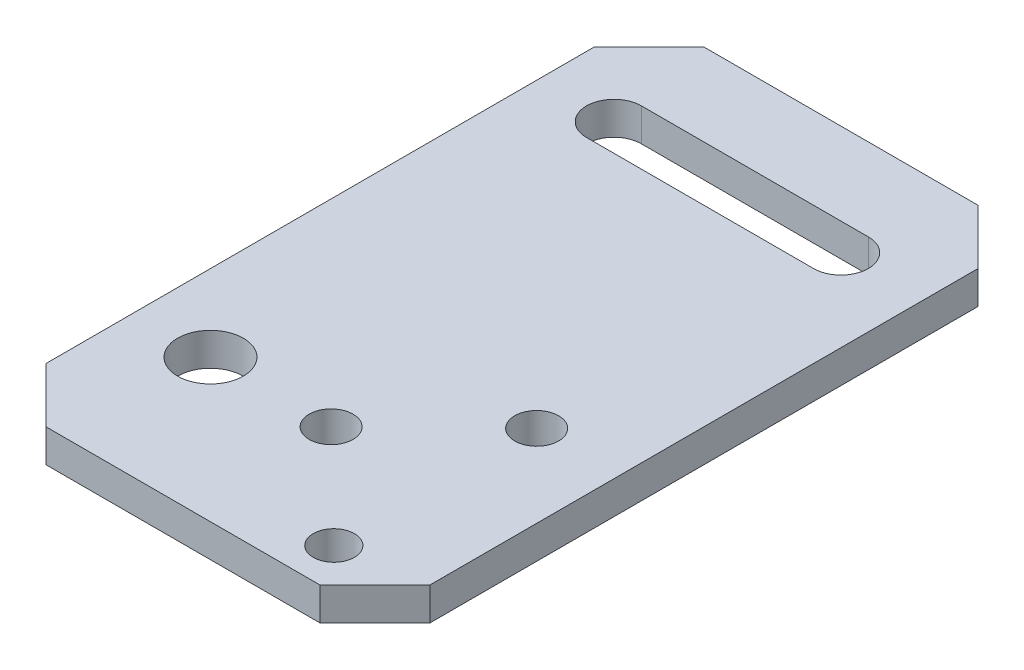
SolidWorks part; units mm, degrees
ref_plane "Alzado" through (0, 0, 0) normal (0, 0, 1) x (1, 0, 0)
ref_plane "Planta" through (0, 0, 0) normal (0, 1, 0) x (1, 0, 0)
ref_plane "Vista lateral" through (0, 0, 0) normal (1, 0, 0) x (0, 0, -1)
sketch "Croquis1" plane through (0, 0, 0) normal (0, 1, 0) x (1, 0, 0)
  line L0 (0, 0) -> (0, 34.7658) construction
  line L1 (-17.5, -30) -> (17.5, -30)
  line L2 (-17.5, -30) -> (-17.5, 30)
  line L3 (-17.5, 30) -> (17.5, 30)
  line L4 (17.5, -30) -> (17.5, 30)
  line L5 (-17.5, -30) -> (17.5, 30) construction
  line L6 (-17.5, 30) -> (17.5, -30) construction
  line L7 (10, -7.75) -> (10, -26.25) construction
  line L8 (-10.7, 17.5) -> (10, 17.5)
  line L9 (-10.7, 22.5) -> (10, 22.5)
  arc A0 (-10.7, 22.5) -> (-10.7, 17.5) centre (-10.7, 20) ccw
  arc A1 (10, 17.5) -> (10, 22.5) centre (10, 20) ccw
  circle A4 centre (-10.5, -17) radius 3
  circle A5 centre (0.5, -17) radius 2
  circle A6 centre (10, -7.75) radius 2
  circle A7 centre (10, -26.25) radius 1.8784
  point P0 (0, 0)
  point P7 (-16.9975, -30)
  point P9 (17.1721, -30.0442)
  point P10 (17.5, -30)
  point P13 (-16.1243, 28.8981)
  point P14 (17.7542, -29.5203)
  point P15 (17.8129, 33.1497)
  point P16 (17.55, 29.9128)
  point P17 (-17.6378, -29.7625)
  point P26 (10, -17)
  point P27 (-17.3353, 29.7177)
  point P28 (17.5196, 29.9661)
  dimension "D5" = 5
  dimension "D9" = 6
  dimension "D12" = 4
  dimension "D15" = 4
  dimension "D1" = 35
  dimension "D2" = 60
  dimension "D3" = 10.7
  dimension "D4" = 10
  dimension "D6" = 10
  dimension "D8" = 7
  dimension "D10" = 13
  dimension "D11" = 11
  dimension "D13" = 9.5
  dimension "D14" = 18.5
extrude "Saliente-Extruir1" add sketch "Croquis1" along normal blind 3
chamfer "Chaflán1" distance 5 angle 45 4 edges at (17.5, 1.5, 30) (-17.5, 1.5, 30) (17.5, 1.5, -30) (-17.5, 1.5, -30)
